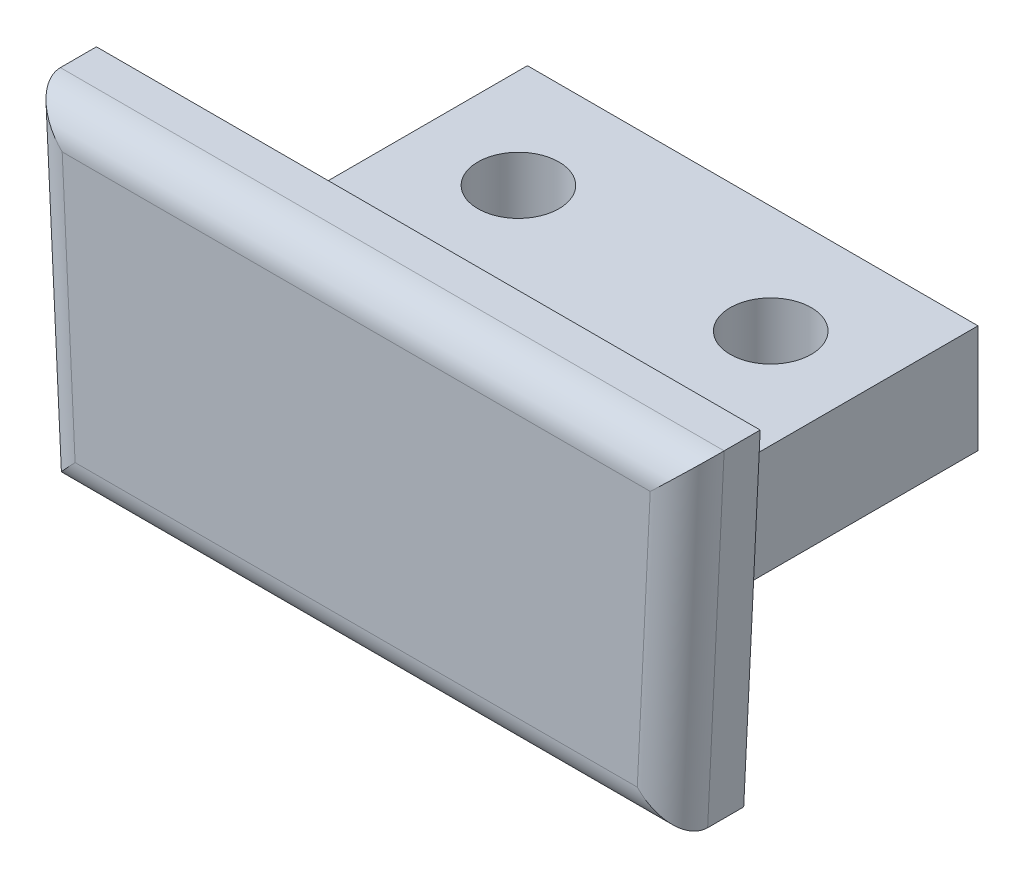
SolidWorks part; units mm, degrees
ref_plane "Front Plane" through (0, 0, 0) normal (0, 0, 1) x (1, 0, 0)
ref_plane "Top Plane" through (0, 0, 0) normal (0, 1, 0) x (1, 0, 0)
ref_plane "Right Plane" through (0, 0, 0) normal (1, 0, 0) x (0, 0, -1)
sketch "Sketch1" plane through (0, 0, 0) normal (0, 1, 0) x (1, 0, 0)
  line L1 (0, 0) -> (25, 0)
  line L2 (0, 0) -> (0, 23)
  line L3 (0, 23) -> (25, 23)
  line L4 (25, 0) -> (25, 23)
  dimension "D1" = 25
  dimension "D2" = 23
extrude "Boss-Extrude1" add sketch "Sketch1" along normal blind 6
sketch "Sketch5" plane through (0, 0, 0) normal (0, 0, 1) x (1, 0, 0)
  line L7 (-5.9133, 12.95) -> (30.915, 12.95)
  line L10 (30, -5.62) -> (30.915, 12.95)
  line L11 (0, 6) -> (25, 6) construction
  line L12 (12.5008, 12.95) -> (12.5, -5.62) construction
  line L13 (-5.9133, 12.95) -> (-5, -5.62)
  line L14 (-5, -5.62) -> (30, -5.62)
  point P10 (12.5, 6)
  dimension "D1" = 35
  dimension "D2" = 36.8283
  dimension "D3" = 6.95
  dimension "D6" = 18.415
extrude "Boss-Extrude3" add sketch "Sketch5" against normal blind 4
fillet "Fillet1" radius 2 4 edges at (12.5008, 12.95, 0) (30.4575, 3.665, 0) (-5.4567, 3.665, 0) (12.5, -5.62, 0)
sketch "Sketch2" plane through (0, 0, 0) normal (0, -1, 0) x (1, 0, 0)
  line L0 (12.5, 0) -> (12.5, -23) construction
  line L1 (0, 0) -> (25, 0) construction
  line L2 (25, -23) -> (0, -23) construction
  line L3 (-5, -4) -> (30, -4) construction
  circle A0 centre (5.5, -16) radius 2.25
  circle A1 centre (19.5, -16) radius 2.25
  dimension "D1" = 7
  dimension "D3" = 4.5
  dimension "D4" = 12
extrude "Cut-Extrude1" cut sketch "Sketch2" against normal blind 6
sketch "Sketch9" plane through (0, 0, -23) normal (0, 0, -1) x (-1, 0, 0)
  line L1 (-25, 6) -> (0, 6)
  line L2 (-25, 6) -> (-25, 0)
  line L3 (-25, 0) -> (0, 0)
  line L4 (0, 6) -> (0, 0)
extrude "Cut-Extrude2" cut sketch "Sketch9" against normal blind 1
